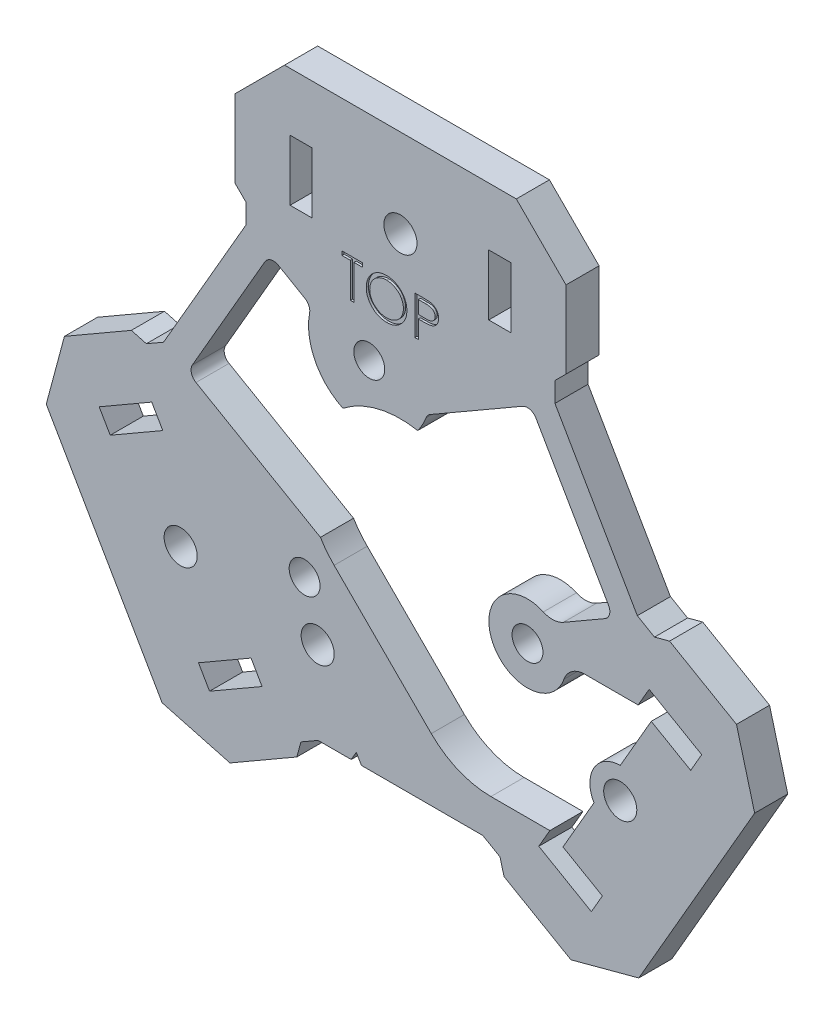
SolidWorks part; units mm, degrees
material "6061-T6 Black anodised"
ref_plane "Front Plane" through (0, 0, 0) normal (0, 0, 1) x (1, 0, 0)
ref_plane "Top Plane" through (0, 0, 0) normal (0, 1, 0) x (1, 0, 0)
ref_plane "Right Plane" through (0, 0, 0) normal (1, 0, 0) x (0, 0, -1)
sketch "Sketch1" plane through (0, 0, 0) normal (0, 0, 1) x (1, 0, 0)
  line L0 (8, 23) -> (8, 25.75)
  line L1 (0, -20.4762) -> (7.4659, -20.4762)
  line L2 (9.0215, -21.3744) -> (7.4659, -20.4762)
  line L3 (9.3875, -22.7404) -> (9.0215, -21.3744)
  line L4 (11.1369, -23.7504) -> (9.3875, -22.7404)
  line L5 (13.6369, -19.4203) -> (11.1369, -23.7504) construction
  line L6 (12.537, -18.7853) -> (13.6369, -19.4203)
  line L7 (8, 25.75) -> (10, 25.75)
  line L8 (10, 25.75) -> (10, 23)
  line L9 (13.537, -17.0532) -> (12.537, -18.7853)
  line L10 (0, 0) -> (0, 23) construction
  line L11 (-15, 23) -> (15, 23) construction
  line L12 (-8, 23) -> (-8, 20.25)
  line L13 (-8, 20.25) -> (-10, 20.25)
  line L14 (10, 20.25) -> (10, 23)
  line L15 (8, 20.25) -> (10, 20.25)
  line L16 (-10, 20.25) -> (-10, 23)
  line L17 (-10, 21.52) -> (-15, 21.52) construction
  line L18 (-15, 23) -> (-15, 19.5)
  line L19 (-15, 19.5) -> (-14, 18.5)
  line L20 (-14, 18.5) -> (-14, 16.7038)
  line L21 (8, 23) -> (8, 20.25)
  line L22 (15.9186, -18.4282) -> (13.537, -17.0532)
  line L23 (-15, 23) -> (-15, 26.5)
  line L24 (15.9186, -18.4282) -> (18.3002, -19.8032)
  line L25 (-10, 24.48) -> (-15, 24.48) construction
  line L26 (-10, 25.75) -> (-10, 23)
  line L27 (18.3002, -19.8032) -> (17.3002, -21.5353)
  line L28 (17.3002, -21.5353) -> (13.6369, -19.4203)
  line L29 (-8, 25.75) -> (-10, 25.75)
  line L30 (-8, 23) -> (-8, 25.75)
  line L31 (0, 23) -> (0, 31) construction
  line L32 (-15, 26.5) -> (-10.5, 31)
  line L33 (-10.5, 31) -> (10.5, 31)
  line L34 (14, 18.5) -> (14, 16.7038)
  line L35 (15, 19.5) -> (14, 18.5)
  line L36 (15, 23) -> (15, 19.5)
  line L37 (10, 21.52) -> (15, 21.52) construction
  line L38 (16.2003, -20.9003) -> (13.7003, -25.2304) construction
  line L39 (11.1369, -23.7504) -> (15.4497, -26.2404)
  line L40 (15.4497, -26.2404) -> (21.5968, -24.5933)
  line L41 (32.0968, -6.4067) -> (21.5968, -24.5933)
  line L42 (30.4497, -0.2596) -> (32.0968, -6.4067)
  line L43 (26.1369, 2.2304) -> (30.4497, -0.2596)
  line L44 (26.2003, -3.5797) -> (28.7003, 0.7504) construction
  line L45 (27.3002, -4.2147) -> (23.6369, -2.0997)
  line L46 (26.3002, -5.9468) -> (27.3002, -4.2147)
  line L47 (23.9186, -4.5718) -> (26.3002, -5.9468)
  line L48 (23.9186, -4.5718) -> (21.537, -3.1968)
  line L49 (21.537, -3.1968) -> (22.537, -1.4647)
  line L50 (22.537, -1.4647) -> (23.6369, -2.0997)
  line L51 (10, 24.48) -> (15, 24.48) construction
  line L52 (15, 23) -> (15, 26.5)
  line L53 (15, 26.5) -> (10.5, 31)
  line L54 (23.6369, -2.0997) -> (26.1369, 2.2304) construction
  line L55 (26.1369, 2.2304) -> (24.3875, 3.2404)
  line L56 (24.3875, 3.2404) -> (23.0215, 2.8744)
  line L57 (23.0215, 2.8744) -> (21.4659, 3.7725)
  line L58 (21.4659, 3.7725) -> (17.7329, 10.2381)
  line L59 (-17.7329, 10.2381) -> (-21.4659, 3.7725)
  line L60 (-23.0215, 2.8744) -> (-21.4659, 3.7725)
  line L61 (-24.3875, 3.2404) -> (-23.0215, 2.8744)
  line L62 (-26.1369, 2.2304) -> (-24.3875, 3.2404)
  line L63 (-23.6369, -2.0997) -> (-26.1369, 2.2304) construction
  line L64 (-22.537, -1.4647) -> (-23.6369, -2.0997)
  line L65 (-21.537, -3.1968) -> (-22.537, -1.4647)
  line L66 (-23.9186, -4.5718) -> (-21.537, -3.1968)
  line L67 (-23.9186, -4.5718) -> (-26.3002, -5.9468)
  line L68 (-26.3002, -5.9468) -> (-27.3002, -4.2147)
  line L69 (-27.3002, -4.2147) -> (-23.6369, -2.0997)
  line L70 (-26.2003, -3.5797) -> (-28.7003, 0.7504) construction
  line L71 (-26.1369, 2.2304) -> (-30.4497, -0.2596)
  line L72 (-30.4497, -0.2596) -> (-32.0968, -6.4067)
  line L73 (-21.5968, -24.5933) -> (-32.0968, -6.4067)
  line L74 (-15.4497, -26.2404) -> (-21.5968, -24.5933)
  line L75 (-11.1369, -23.7504) -> (-15.4497, -26.2404)
  line L76 (-16.2003, -20.9003) -> (-13.7003, -25.2304) construction
  line L77 (-17.3002, -21.5353) -> (-13.6369, -19.4203)
  line L78 (-18.3002, -19.8032) -> (-17.3002, -21.5353)
  line L79 (-15.9186, -18.4282) -> (-18.3002, -19.8032)
  line L80 (-15.9186, -18.4282) -> (-13.537, -17.0532)
  line L81 (-13.537, -17.0532) -> (-12.537, -18.7853)
  line L82 (-12.537, -18.7853) -> (-13.6369, -19.4203)
  line L83 (-13.6369, -19.4203) -> (-11.1369, -23.7504) construction
  line L84 (-11.1369, -23.7504) -> (-9.3875, -22.7404)
  line L85 (-9.3875, -22.7404) -> (-9.0215, -21.3744)
  line L86 (-9.0215, -21.3744) -> (-7.4659, -20.4762)
  line L87 (-7.4659, -20.4762) -> (0, -20.4762)
  line L136 (-14, 16.7038) -> (-17.7329, 10.2381)
  line L138 (17.7329, 10.2381) -> (14, 16.7038)
  line L139 (0, 0) -> (0, -20.4762) construction
  line L140 (0, 0) -> (17.7329, 10.2381) construction
  line L141 (0, 0) -> (-17.7329, 10.2381) construction
  circle A0 centre (0, 23) radius 1.5
  circle A1 centre (19.9186, -11.5) radius 1.5
  circle A2 centre (0, 0) radius 1.6 construction
  circle A3 centre (-19.9186, -11.5) radius 1.5
  point P0 (0, 0)
  point P32 (-8, 23)
  point P102 (0, 0)
  point P108 (0, 0)
  point P148 (0, 0)
  dimension "D4" = 3
  dimension "D5" = 3
  dimension "D2" = 120
  dimension "D3" = 2
  dimension "D6" = 5
  dimension "D7" = 1.48
  dimension "D8" = 3
  dimension "D9" = 5.5
  dimension "D11" = 30
  dimension "D14" = 23
  dimension "D15" = 7
  dimension "D16" = 45
  dimension "D17" = 8
  dimension "D18" = 1
extrude "Boss-Extrude1" add sketch "Sketch1" along normal blind 3
ref_axis "Axis1" through (0, 0, -0.15) along (0, 0, 1)
sketch "Sketch3" plane through (0, 0, 3) normal (0, 0, 1) x (1, 0, 0)
  line L1 (-14, 14) -> (14, 14) construction
  line L2 (-14, 14) -> (-14, -14) construction
  line L3 (-14, -14) -> (14, -14) construction
  line L4 (14, 14) -> (14, -14) construction
  line L5 (-14, 14) -> (14, -14) construction
  line L6 (-14, -14) -> (14, 14) construction
  circle A0 centre (0, 0) radius 8.5
  circle A1 centre (-14, -14) radius 1.6 construction
  circle A2 centre (-14, 14) radius 1.6 construction
  circle A3 centre (14, 14) radius 1.6 construction
  circle A4 centre (14, -14) radius 1.6 construction
  dimension "D1" = 3.2
  dimension "D3" = 17
  dimension "D2" = 28
extrude "Cut-Extrude2" cut sketch "Sketch3" against normal through all
sketch "Sketch4" plane through (0, 0, 3) normal (0, 0, 1) x (1, 0, 0)
  line L0 (-15, 0) -> (0, 0) construction
  line L1 (7.5, 12.9904) -> (-7.5, 12.9904) construction
  line L2 (-7.5, 12.9904) -> (-15, 0) construction
  line L3 (-15, 0) -> (-7.5, -12.9904) construction
  line L4 (-7.5, -12.9904) -> (7.5, -12.9904) construction
  line L5 (7.5, -12.9904) -> (15, 0) construction
  line L6 (15, 0) -> (7.5, 12.9904) construction
  line L7 (0, 0) -> (11.5136, -3.3819) construction
  line L8 (0, 0) -> (6.0104, 6.0104) construction
  line L9 (-8.6856, -8.2801) -> (0, 0) construction
  line L10 (12.3355, -0.3146) -> (9.2682, -1.1365) construction
  line L11 (9.2682, -1.1365) -> (8.4464, -4.2037) construction
  line L12 (8.4464, -4.2037) -> (10.6917, -6.4491) construction
  line L13 (10.6917, -6.4491) -> (13.759, -5.6272) construction
  line L14 (13.759, -5.6272) -> (14.5808, -2.56) construction
  line L15 (14.5808, -2.56) -> (12.3355, -0.3146) construction
  line L16 (6.0104, 6.0104) -> (19.3596, -7.3388) construction
  line L17 (-7.4659, -20.4762) -> (7.4659, -20.4762) construction
  circle A0 centre (0, 0) radius 12.9904 construction
  circle A1 centre (-7.5, 12.9904) radius 1.5 construction
  circle A2 centre (7.5, 12.9904) radius 1.5 construction
  circle A3 centre (15, 0) radius 1.5 construction
  circle A4 centre (7.5, -12.9904) radius 1.5 construction
  circle A5 centre (-7.5, -12.9904) radius 1.5
  circle A6 centre (-15, 0) radius 1.5 construction
  circle A7 centre (-2.828, 11.662) radius 1.4
  circle A8 centre (11.5136, -3.3819) radius 1.4
  circle A9 centre (-8.6856, -8.2801) radius 1.4
  circle A10 centre (0, 0) radius 8.5 construction
  circle A11 centre (11.5136, -3.3819) radius 2.75 construction
  circle A12 centre (-8.6856, -8.2801) radius 3.5 construction
  point P22 (0, 0)
  point P31 (0, 0)
  dimension "D2" = 3
  dimension "D4" = 17
  dimension "D5" = 7
  dimension "D6" = 2.8
  dimension "D8" = 5.5
  dimension "D1" = 15
  dimension "D9" = 12
  dimension "D10" = 45
  dimension "D3" = 6
  dimension "D7" = 3
extrude "Cut-Extrude3" cut sketch "Sketch4" against normal through all
sketch "Sketch6" plane through (0, 0, 3) normal (0, 0, 1) x (1, 0, 0)
  line L1 (-6.8026, 6.8026) -> (0, 0) construction
  line L2 (12.2799, 14.683) -> (18.8558, 3.2932)
  line L3 (0, 0) -> (0, -8.5) construction
  line L4 (13.537, -17.0532) -> (21.537, -3.1968) construction
  line L5 (13.537, -17.0532) -> (12.537, -18.7853) construction
  line L6 (21.537, -3.1968) -> (16.7055, -3.1968)
  line L7 (0, 0) -> (8.5, 0) construction
  line L8 (13.537, -17.0532) -> (8.1976, -17.0532)
  line L9 (19.9186, -8.75) -> (22.7278, -3.8843)
  line L10 (2.7943, -14.8151) -> (-6.0104, -6.0104)
  line L11 (21.537, -3.1968) -> (26.3002, -5.9468) construction
  line L12 (22.7278, -3.8843) -> (21.537, -3.1968)
  line L13 (17.537, -12.875) -> (14.7278, -17.7407)
  line L14 (18.3002, -19.8032) -> (13.537, -17.0532) construction
  line L15 (14.7278, -17.7407) -> (13.537, -17.0532)
  line L21 (18.5301, 2.0775) -> (14.7655, -0.096)
  line L22 (11.0642, 15.0088) -> (2.7084, 10.1846)
  line L23 (21.4659, 3.7725) -> (14, 16.7038) construction
  line L25 (8.1976, -2.2472) -> (8.1976, -17.6) construction
  line L27 (-11.0642, 15.0088) -> (-8.6615, 13.6216)
  line L28 (-12.2799, 14.683) -> (-18.8558, 3.2932)
  line L29 (-18.5301, 2.0775) -> (-7.2519, -4.434)
  line L30 (-14, 16.7038) -> (-21.4659, 3.7725) construction
  arc A0 (19.9186, -8.75) -> (17.537, -12.875) centre (19.9186, -11.5) ccw
  circle A1 centre (0, 0) radius 8.5 construction
  arc A2 (-8.232, 12.6852) -> (-5.2192, 6.709) centre (-2.828, 11.662) ccw
  arc A3 (8.1976, -17.0532) -> (2.7943, -14.8151) centre (8.1976, -9.4118) cw
  circle A4 centre (0, 0) radius 8.5 construction
  circle A5 centre (0, 0) radius 2.6 construction
  arc A6 (8.1976, -2.2472) -> (8.5, 0) centre (0, 0) ccw construction
  arc A7 (1.5663, 8.3544) -> (2.3203, 9.727) centre (-2.828, 11.662) ccw
  arc A8 (12.9466, -0.1887) -> (14.8175, -4.5368) centre (11.5136, -3.3819) ccw
  arc A9 (16.7055, -3.1968) -> (14.8175, -4.5368) centre (16.7055, -5.1968) ccw
  arc A10 (12.2799, 14.683) -> (11.0642, 15.0088) centre (11.5092, 14.238) ccw
  arc A11 (18.5301, 2.0775) -> (18.8558, 3.2932) centre (18.0851, 2.8482) ccw
  arc A12 (-11.0642, 15.0088) -> (-12.2799, 14.683) centre (-11.5092, 14.238) ccw
  arc A13 (-18.8558, 3.2932) -> (-18.5301, 2.0775) centre (-18.0851, 2.8482) ccw
  arc A14 (-8.6615, 13.6216) -> (-8.232, 12.6852) centre (-9.1065, 12.8508) cw
  arc A15 (-7.2519, -4.434) -> (-6.0104, -6.0104) centre (0, 0) ccw
  arc A16 (12.9466, -0.1887) -> (14.7655, -0.096) centre (13.7655, 1.636) ccw
  arc A17 (1.5663, 8.3544) -> (-5.2192, 6.709) centre (0, 0) ccw
  arc A18 (2.7084, 10.1846) -> (2.3203, 9.727) centre (3.1534, 9.4138) ccw
  point P27 (31.1865, -12.0167)
  point P28 (23.7865, 0.8005)
  point P29 (15.2995, -4.0995)
  point P30 (22.6995, -16.9167)
  dimension "D7" = 5.2
  dimension "D4" = 11
  dimension "D5" = 0.89
  dimension "D6" = 2
  dimension "D1" = 135
  dimension "D2" = 2.5
  dimension "D3" = 2.5
extrude "Cut-Extrude4" cut sketch "Sketch6" against normal through all
sketch "Sketch7" plane through (0, 0, 3) normal (0, 0, 1) x (1, 0, 0)
  line L2 (-10, 28) -> (10, 28)
  line L3 (-10, 28) -> (-10, 48)
  line L4 (-10, 48) -> (10, 48)
  line L5 (10, 28) -> (10, 48)
  line L6 (-10, 28) -> (10, 48) construction
  line L7 (-10, 48) -> (10, 28) construction
  circle A0 centre (0, 23) radius 1.5 construction
  dimension "D1" = 5
  dimension "D3" = 20
extrude "Cut-Extrude5" [suppressed] cut sketch "Sketch7" against normal through all
sketch "Sketch8" plane through (0, 0, 3) normal (0, 0, 1) x (1, 0, 0)
  line L0 (-4.4619, -20.4762) -> (-4, -19.6762)
  line L1 (-7.4659, -20.4762) -> (7.4659, -20.4762) construction
  line L2 (-4, -19.6762) -> (-3.5381, -20.4762)
  line L3 (-3.5381, -20.4762) -> (-4.4619, -20.4762)
  dimension "D1" = 4
  dimension "D2" = 0.8
extrude "Cut-Extrude6" cut sketch "Sketch8" against normal through all
sketch "Sketch9" plane through (0, 0, 3) normal (0, 0, 1) x (1, 0, 0)
  text T0 "TOP"
extrude "Cut-Extrude7" cut sketch "Sketch9" against normal blind 0.2
equation "\"D3@Sketch6\"=\"D2@Sketch6\""
